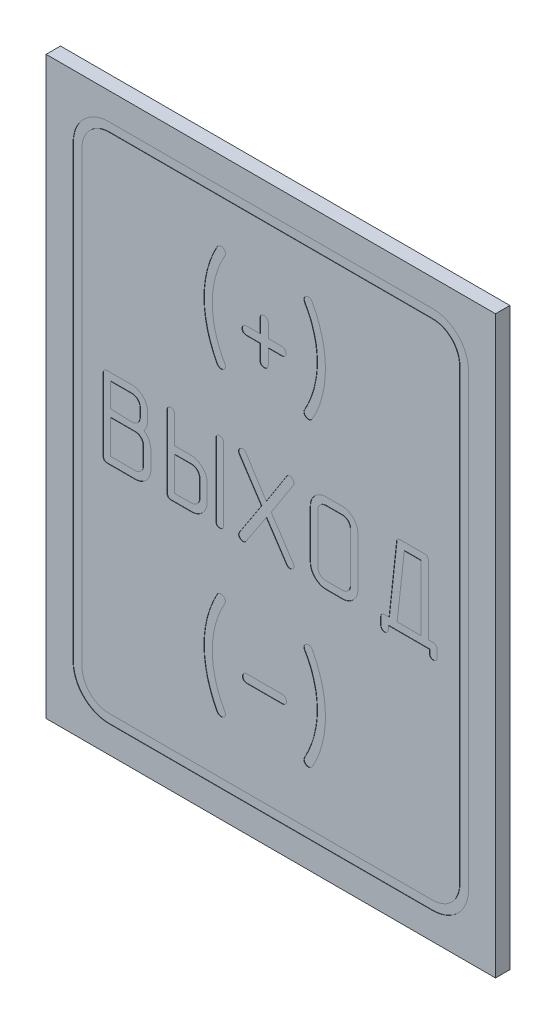
SolidWorks part; units mm, degrees
ref_plane "Спереди" through (0, 0, 0) normal (0, 0, 1) x (1, 0, 0)
ref_plane "Сверху" through (0, 0, 0) normal (0, 1, 0) x (1, 0, 0)
ref_plane "Справа" through (0, 0, 0) normal (1, 0, 0) x (0, 0, -1)
sketch "Эскиз1" plane through (0, 0, 0) normal (0, 0, 1) x (1, 0, 0)
  line L0 (-35.1079, 0) -> (45.1386, 0) construction
  line L1 (0, 44.73) -> (0, -45.9337) construction
  line L3 (-12.5, -16) -> (12.5, -16)
  line L4 (-12.5, -16) -> (-12.5, 16)
  line L5 (-12.5, 16) -> (12.5, 16)
  line L6 (12.5, -16) -> (12.5, 16)
  dimension "D1" = 25
  dimension "D2" = 32
extrude "Вытянуть1" add sketch "Эскиз1" along normal blind 0.8
sketch "Эскиз2" plane through (0, 0, 0.8) normal (0, 0, 1) x (1, 0, 0)
  line L0 (12.5, 16) -> (-12.5, 16) construction
  line L1 (-9, -14) -> (9, -14)
  line L2 (-10.5, -12.5) -> (-10.5, 12.5)
  line L3 (-9, 14) -> (9, 14)
  line L4 (10.5, -12.5) -> (10.5, 12.5)
  line L5 (-12.5, 16) -> (-12.5, -16) construction
  line L6 (12.5, -16) -> (12.5, 16) construction
  line L7 (-12.5, -16) -> (12.5, -16) construction
  arc A0 (-10.5, 12.5) -> (-9, 14) centre (-9, 12.5) cw
  arc A1 (9, 14) -> (10.5, 12.5) centre (9, 12.5) cw
  arc A2 (9, -14) -> (10.5, -12.5) centre (9, -12.5) ccw
  arc A3 (-9, -14) -> (-10.5, -12.5) centre (-9, -12.5) cw
  dimension "D5" = 1.5
  dimension "D1" = 2
  dimension "D2" = 2
  dimension "D3" = 2
  dimension "D4" = 2
extrude "Вырез-Вытянуть-Тонкостенный1" cut sketch "Эскиз2" against normal blind 0.02 and the other way blind 0.02 thin thin type one direction wall 0.5
sketch "Эскиз3" plane through (0, 0, 0.8) normal (0, 0, 1) x (1, 0, 0)
  line L0 (-12.5, -16) -> (12.5, -16) construction
  line L1 (-12.5, 16) -> (-12.5, -16) construction
  text T0 "ВЫХОД" font "GOST type B" height 4.5
  text T1 "(+)" font "GOST type B" height 5
  text T2 "(-)" font "GOST type B" height 5
  dimension "D1" = 14
  dimension "D2" = 2.75
  dimension "D3" = 22.5
  dimension "D4" = 8.25
  dimension "D5" = 8.25
  dimension "D6" = 5.75
extrude "Вырез-Вытянуть1" cut sketch "Эскиз3" against normal blind 0.02
